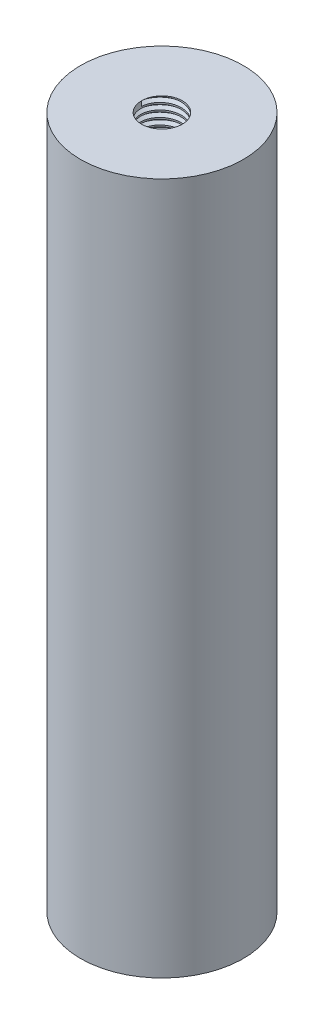
SolidWorks part; units mm, degrees
ref_plane "Front Plane" through (0, 0, 0) normal (0, 0, 1) x (1, 0, 0)
ref_plane "Top Plane" through (0, 0, 0) normal (0, 1, 0) x (1, 0, 0)
ref_plane "Right Plane" through (0, 0, 0) normal (1, 0, 0) x (0, 0, -1)
sketch "Sketch1" plane through (0, 0, 0) normal (0, 1, 0) x (1, 0, 0)
  circle A0 centre (0, 0) radius 10
extrude "Boss-Extrude1" add sketch "Sketch1" along normal blind 85
sketch "Sketch2" plane through (0, 0, 0) normal (0, -1, 0) x (-1, 0, 0)
  circle A0 centre (0, 0) radius 2.5
extrude "Cut-Extrude1" cut sketch "Sketch2" against normal blind 20 contours A0
sketch "Sketch3" plane through (0, 85, 0) normal (0, 1, 0) x (1, 0, 0)
  circle A0 centre (0, 0) radius 2.5
extrude "Cut-Extrude2" cut sketch "Sketch3" against normal blind 20
thread "Thread1" pitch 0.8 start angle 0, offset 0, length 0, pitch 0.8, diameter 5
ref_plane "Plane1" through (2.5, 0, 0) normal (0, 0, 1) x (1, 0, 0)
sketch "Thread Profile1" plane through (2.5, 0, 0) normal (0, 0, 1) x (1, 0, 0)
  line L0 (0, 0) -> (0, 0.8) construction
  line L1 (0, 0) -> (0.433, 0.25)
  line L2 (0.433, 0.25) -> (0.433, 0.35)
  line L3 (0.433, 0.35) -> (0, 0.6)
  line L4 (0.433, 0.3) -> (0, 0.3) construction
  line L11 (0, 0) -> (0, 0.6)
  point P2 (0, 0)
  dimension "Pitch" = 0.8
  dimension "Profile_Angle" = 60
  dimension "Profile_Land" = 0.1
  dimension "Profile_Height" = 0.433
thread "Thread2" pitch 0.8 profile "Thread Profile2" start angle 0, offset 0, length 0, pitch 0.8, diameter 5
ref_plane "Plane2" through (-2.5, 85, 0) normal (0, 0, 1) x (-1, 0, 0)
sketch "Thread Profile2" plane through (-2.5, 85, 0) normal (0, 0, 1) x (-1, 0, 0)
  line L0 (0, 0) -> (0, 0.8) construction
  line L1 (0, 0) -> (0.433, 0.25)
  line L2 (0.433, 0.25) -> (0.433, 0.35)
  line L3 (0.433, 0.35) -> (0, 0.6)
  line L4 (0.433, 0.3) -> (0, 0.3) construction
  line L11 (0, 0) -> (0, 0.6)
  point P2 (0, 0)
  dimension "Pitch" = 0.8
  dimension "Profile_Angle" = 60
  dimension "Profile_Land" = 0.1
  dimension "Profile_Height" = 0.433
